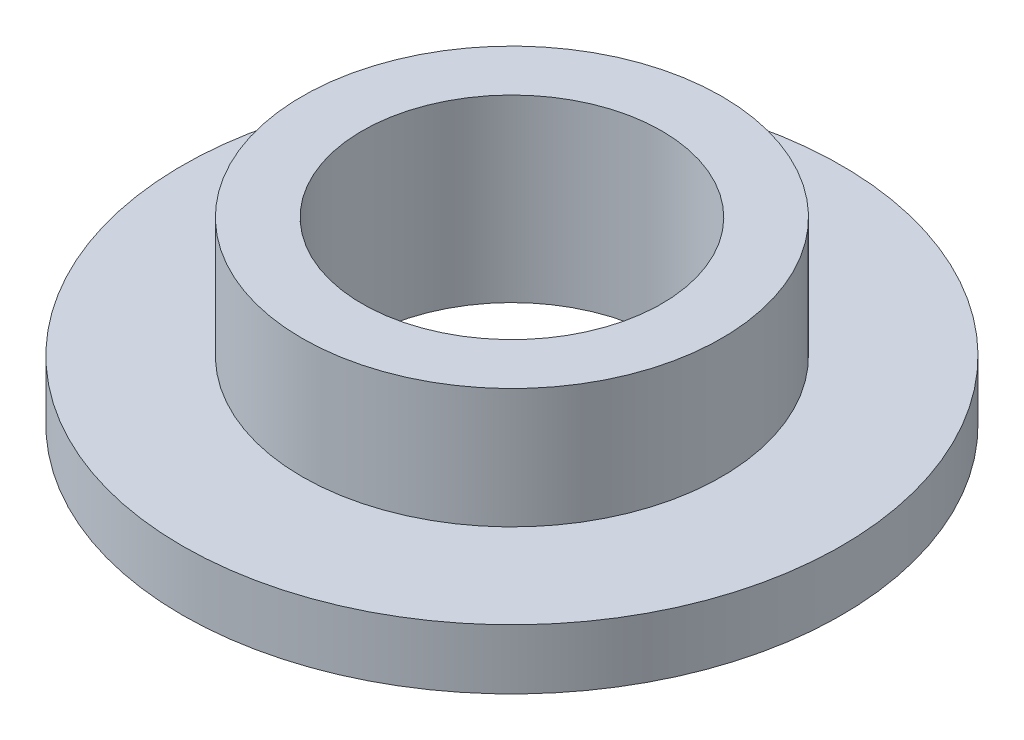
SolidWorks part; units mm, degrees
ref_plane "Front" through (0, 0, 0) normal (0, 0, 1) x (1, 0, 0)
ref_plane "Top" through (0, 0, 0) normal (0, 1, 0) x (1, 0, 0)
ref_plane "Right" through (0, 0, 0) normal (1, 0, 0) x (0, 0, -1)
sketch "Sketch1" plane through (0, 0, 0) normal (0, 1, 0) x (1, 0, 0)
  line L0 (0, 2.5) -> (0, 3.5) construction
  line L1 (2.5, 0) -> (-2.5, 0) construction
  line L2 (0, 5.5) -> (0, -5.5) construction
  line L3 (-3.5, 0) -> (3.5, 0) construction
  circle A0 centre (0, 0) radius 2.5
  circle A1 centre (0, 0) radius 3.5
  circle A2 centre (0, 0) radius 5.5
  point P10 (0, 0)
  point P11 (0, 0)
  point P12 (0, 0)
  point P18 (0, 2.5)
  point P19 (0, -2.5)
  dimension "ID" = 5
  dimension "OD" = 7
  dimension "FlangeOD" = 11
sketch "Sketch2" plane through (0, 0, 0) normal (1, 0, 0) x (0, 0, -1)
  line L0 (0, 0) -> (0, 3) construction
  line L1 (0, 3) -> (3.5, 3) construction
  line L2 (3.5, 3) -> (3.5, 0) construction
  line L3 (-5.5, 0) -> (-5.5, 1) construction
  line L4 (5.5, 0) -> (-5.5, 0) construction
  line L5 (2.5, 0) -> (2.5, 3) construction
  line L7 (-2.5, 0) -> (-2.5, 3) construction
  dimension "Length" = 3
  dimension "Flange" = 1
sketch "Sketch5" plane through (0, 0, 0) normal (1, 0, 0) x (0, 0, -1)
  line L0 (3.5, 3) -> (3.5, 0)
  line L1 (3.5, 0) -> (2.5, 0)
  line L2 (2.5, 0) -> (2.5, 3)
  line L3 (2.5, 3) -> (3.5, 3)
revolve "Revolve1" add sketch "Sketch5" angle 360 about L0
sketch "Sketch3" plane through (0, 0, 0) normal (0, 1, 0) x (1, 0, 0)
  circle A0 centre (0, 0) radius 5.5 construction
  circle A1 centre (0, 0) radius 3.5 construction
  circle A2 centre (0, 0) radius 5.5
  circle A3 centre (0, 0) radius 3.5
extrude "Boss-Extrude2" add sketch "Sketch3" along normal up to vertex (1 mm away) up to point (0, 1, 5.5)
ref_plane "Contact Plane 1" through (0, 3, 0) normal (0, 1, 0) x (1, 0, 0)
ref_plane "Contact Plane 2" through (0, 0, 0) normal (0, -1, 0) x (-1, 0, 0)
ref_axis "Center Axis 1" through (0, 0, 0) along (0, 1, 0)
